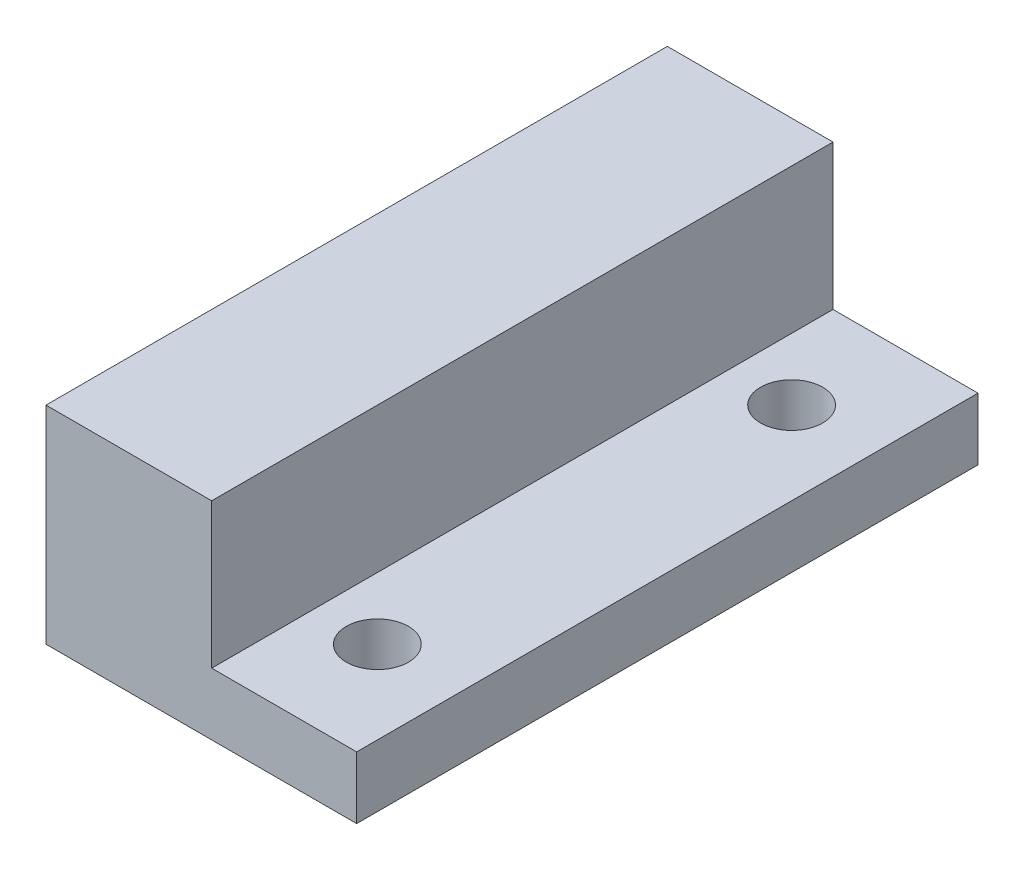
SolidWorks part; units mm, degrees
ref_plane "Front Plane" through (0, 0, 0) normal (0, 0, 1) x (1, 0, 0)
ref_plane "Top Plane" through (0, 0, 0) normal (0, 1, 0) x (1, 0, 0)
ref_plane "Right Plane" through (0, 0, 0) normal (1, 0, 0) x (0, 0, -1)
sketch "Sketch1" plane through (0, 0, 0) normal (0, 1, 0) x (1, 0, 0)
  line L0 (0, 0) -> (0, -25.4) construction
  line L1 (-13.97, 6.35) -> (5.08, 6.35)
  line L2 (-13.97, 6.35) -> (-13.97, -31.75)
  line L3 (-13.97, -31.75) -> (5.08, -31.75)
  line L4 (5.08, 6.35) -> (5.08, -31.75)
  circle A0 centre (0, 0) radius 1.905
  circle A1 centre (0, -25.4) radius 1.905
  point P6 (-13.97, -12.7)
  point P11 (0, 0)
  point P12 (0, -12.7)
  point P13 (0, 0)
  dimension "D1" = 25.4
  dimension "D2" = 3.81
  dimension "D3" = 3.81
  dimension "D4" = 5.08
  dimension "D5" = 38.1
  dimension "D6" = 19.05
extrude "Boss-Extrude1" add sketch "Sketch1" along normal blind 3.81
sketch "Sketch2" plane through (0, 3.81, 0) normal (0, 1, 0) x (1, 0, 0)
  line L0 (-13.97, 6.35) -> (-13.97, -31.75)
  line L1 (-13.97, -31.75) -> (-3.81, -31.75)
  line L2 (-13.97, -31.75) -> (5.08, -31.75) construction
  line L3 (-3.81, -31.75) -> (-3.81, 6.35)
  line L4 (5.08, 6.35) -> (-13.97, 6.35) construction
  line L5 (-3.81, 6.35) -> (-6.35, 6.35)
  line L6 (-6.35, 6.35) -> (-6.35, -29.21)
  line L7 (-6.35, -29.21) -> (-11.43, -29.21)
  line L8 (-11.43, -29.21) -> (-11.43, 6.35)
  line L9 (-11.43, 6.35) -> (-13.97, 6.35)
  dimension "D1" = 2.54
  dimension "D2" = 5.08
  dimension "D3" = 2.54
extrude "Boss-Extrude2" add sketch "Sketch2" along normal blind 6.35 contours L0 L1 L3 L5 L6 L7 L8 L9
sketch "Sketch3" plane through (0, 10.16, 0) normal (0, 1, 0) x (1, 0, 0)
  line L1 (-13.97, 6.35) -> (-3.81, 6.35)
  line L2 (-13.97, 6.35) -> (-13.97, -31.75)
  line L3 (-13.97, -31.75) -> (-3.81, -31.75)
  line L4 (-3.81, 6.35) -> (-3.81, -31.75)
extrude "Boss-Extrude3" add sketch "Sketch3" along normal blind 2.54
chamfer "Chamfer1" distance 1.27 angle 45 2 edges at (-6.35, 10.16, 11.43) (-11.43, 10.16, 11.43)
